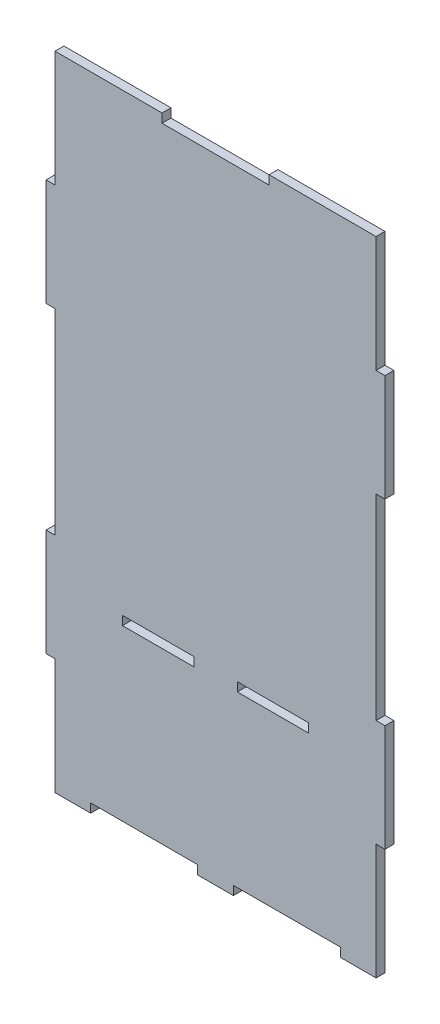
SolidWorks part; units mm, degrees
ref_plane "Front Plane" through (0, 0, 0) normal (0, 0, 1) x (1, 0, 0)
ref_plane "Top Plane" through (0, 0, 0) normal (0, 1, 0) x (1, 0, 0)
ref_plane "Right Plane" through (0, 0, 0) normal (1, 0, 0) x (0, 0, -1)
sketch "Sketch1" plane through (0, 0, 0) normal (0, 0, 1) x (1, 0, 0)
  line L1 (-192.6077, 179.9617) -> (35.9923, 179.9617)
  line L2 (-192.6077, 179.9617) -> (-192.6077, -277.2383)
  line L3 (-192.6077, -277.2383) -> (35.9923, -277.2383)
  line L4 (35.9923, 179.9617) -> (35.9923, -277.2383)
  dimension "D1" = 457.2
  dimension "D2" = 228.6
extrude "Boss-Extrude1" add sketch "Sketch1" along normal blind 6.35
sketch "Sketch2" plane through (0, 0, 6.35) normal (0, 0, 1) x (1, 0, 0)
  line L0 (-192.6077, 179.9617) -> (-192.6077, -277.2383) construction
  line L1 (-198.9577, 97.4117) -> (-192.6077, 97.4117)
  line L2 (-198.9577, 97.4117) -> (-198.9577, 21.2117)
  line L3 (-198.9577, 21.2117) -> (-192.6077, 21.2117)
  line L4 (-192.6077, 97.4117) -> (-192.6077, 21.2117)
  line L6 (-198.9577, -118.4883) -> (-192.6077, -118.4883)
  line L7 (-198.9577, -118.4883) -> (-198.9577, -194.6883)
  line L8 (-198.9577, -194.6883) -> (-192.6077, -194.6883)
  line L9 (-192.6077, -118.4883) -> (-192.6077, -194.6883)
  line L10 (-78.3077, 179.9617) -> (-78.3077, -277.2383) construction
  line L11 (35.9923, 179.9617) -> (-192.6077, 179.9617) construction
  line L12 (-192.6077, -277.2383) -> (35.9923, -277.2383) construction
  line L13 (42.3423, -194.6883) -> (35.9923, -194.6883)
  line L14 (42.3423, -118.4883) -> (42.3423, -194.6883)
  line L15 (35.9923, -118.4883) -> (35.9923, -194.6883)
  line L16 (42.3423, -118.4883) -> (35.9923, -118.4883)
  line L17 (42.3423, 21.2117) -> (35.9923, 21.2117)
  line L18 (42.3423, 97.4117) -> (42.3423, 21.2117)
  line L19 (35.9923, 97.4117) -> (35.9923, 21.2117)
  line L20 (42.3423, 97.4117) -> (35.9923, 97.4117)
  dimension "D1" = 82.55
  dimension "D2" = 76.2
  dimension "D4" = 82.55
  dimension "D5" = 6.35
extrude "Boss-Extrude4" add sketch "Sketch2" against normal through all
sketch "Sketch3" plane through (0, 0, 6.35) normal (0, 0, 1) x (1, 0, 0)
  line L0 (-192.6077, -277.2383) -> (35.9923, -277.2383) construction
  line L1 (-167.2077, -277.2383) -> (-91.0077, -277.2383)
  line L2 (-167.2077, -277.2383) -> (-167.2077, -270.8883)
  line L3 (-167.2077, -270.8883) -> (-91.0077, -270.8883)
  line L4 (-91.0077, -277.2383) -> (-91.0077, -270.8883)
  line L5 (-78.3077, 179.9617) -> (-78.3077, -277.2383) construction
  line L6 (35.9923, 179.9617) -> (-192.6077, 179.9617) construction
  line L7 (-65.6077, -277.2383) -> (-65.6077, -270.8883)
  line L8 (10.5923, -277.2383) -> (10.5923, -270.8883)
  line L9 (10.5923, -277.2383) -> (-65.6077, -277.2383)
  line L10 (10.5923, -270.8883) -> (-65.6077, -270.8883)
  line L11 (35.9923, 97.4117) -> (35.9923, 179.9617) construction
  line L12 (-116.4077, 179.9617) -> (-40.2077, 179.9617)
  line L13 (-116.4077, 179.9617) -> (-116.4077, 173.6117)
  line L14 (-116.4077, 173.6117) -> (-40.2077, 173.6117)
  line L15 (-40.2077, 179.9617) -> (-40.2077, 173.6117)
  dimension "D2" = 76.2
  dimension "D5" = 6.35
  dimension "D3" = 6.35
  dimension "D1" = 25.4
  dimension "D6" = 76.2
extrude "Cut-Extrude1" cut sketch "Sketch3" against normal blind 6.35
sketch "Sketch4" plane through (0, 0, 0) normal (0, 0, 1) x (1, 0, 0)
  line L3 (-144.6017, -143.8883) -> (-93.8017, -143.8883)
  line L4 (-144.6017, -143.8883) -> (-144.6017, -150.2383)
  line L5 (-144.6017, -150.2383) -> (-93.8017, -150.2383)
  line L6 (-93.8017, -143.8883) -> (-93.8017, -150.2383)
  line L7 (-78.3077, 173.6117) -> (-78.3077, -278.1638) construction
  line L8 (-116.4077, 173.6117) -> (-40.2077, 173.6117) construction
  line L9 (-62.8137, -143.8883) -> (-62.8137, -150.2383)
  line L10 (-12.0137, -150.2383) -> (-62.8137, -150.2383)
  line L11 (-12.0137, -143.8883) -> (-12.0137, -150.2383)
  line L12 (-12.0137, -143.8883) -> (-62.8137, -143.8883)
  line L14 (-91.0077, -277.2383) -> (-65.6077, -277.2383) construction
  dimension "D3" = 15.494
  dimension "D4" = 127
extrude "Cut-Extrude5" cut sketch "Sketch4" against normal through all and the other way through all
equation "\"width\"= 9in"
equation "\"Height\"= 18in"
equation "\"thick\"= 0.25"
equation "\"D1@Sketch1\"=\"Height\""
equation "\"D2@Sketch1\"=\"width\""
equation "\"D1@Boss-Extrude1\"=\"thick\""
equation "\"D5@Sketch2\"=\"thick\""
equation "\"D1\"= \"thick\""
equation "\"D3@Sketch3\"=\"thick\""
equation "\"D1@Cut-Extrude1\"=\"thick\""
equation "\"D5@Sketch3\"=\"thick\""
equation "\"D2@Sketch4\"=\"thick\""
